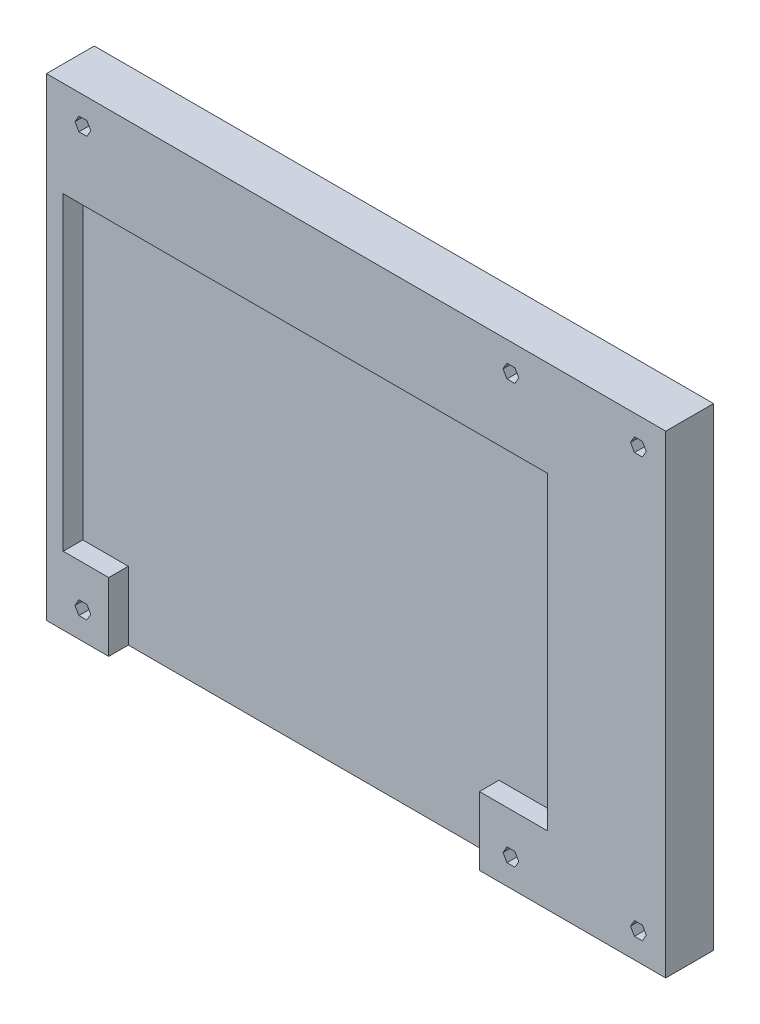
SolidWorks part; units mm, degrees
ref_plane "前视基准面" through (0, 0, 0) normal (0, 0, 1) x (1, 0, 0)
ref_plane "上视基准面" through (0, 0, 0) normal (0, 1, 0) x (1, 0, 0)
ref_plane "右视基准面" through (0, 0, 0) normal (1, 0, 0) x (0, 0, -1)
sketch "草图1" plane through (0, 0, 0) normal (0, 0, 1) x (1, 0, 0)
  line L0 (8, 104) -> (8, 0) construction
  line L1 (0, 0) -> (136, 0)
  line L2 (0, 0) -> (0, 104)
  line L3 (0, 104) -> (136, 104)
  line L4 (136, 0) -> (136, 104)
  line L5 (0, 6) -> (136, 6) construction
  line L6 (0, 98) -> (136, 98) construction
  line L7 (130, 104) -> (130, 0) construction
  line L9 (7.38, 80.5) -> (106.38, 80.5) construction
  line L10 (7.38, 80.5) -> (7.38, 23.5) construction
  line L11 (7.38, 23.5) -> (106.38, 23.5) construction
  line L12 (106.38, 80.5) -> (106.38, 23.5) construction
  line L13 (7.38, 80.5) -> (106.38, 23.5) construction
  line L14 (7.38, 23.5) -> (106.38, 80.5) construction
  line L19 (3.68, 83) -> (110.08, 83)
  line L20 (3.68, 83) -> (3.68, 15)
  line L21 (3.68, 15) -> (110.08, 15)
  line L22 (110.08, 83) -> (110.08, 15)
  line L23 (3.68, 83) -> (110.08, 15) construction
  line L24 (3.68, 15) -> (110.08, 83) construction
  line L25 (13.68, 15) -> (95.08, 15)
  line L26 (13.68, 15) -> (13.68, 0)
  line L27 (13.68, 0) -> (95.08, 0)
  line L28 (95.08, 15) -> (95.08, 0)
  line L29 (13.68, 15) -> (95.08, 0) construction
  line L30 (13.68, 0) -> (95.08, 15) construction
  line L31 (9.7321, 6) -> (8.866, 7.5)
  line L32 (8.866, 7.5) -> (7.134, 7.5)
  line L33 (7.134, 7.5) -> (6.2679, 6)
  line L34 (6.2679, 6) -> (7.134, 4.5)
  line L35 (7.134, 4.5) -> (8.866, 4.5)
  line L36 (8.866, 4.5) -> (9.7321, 6)
  line L37 (128.2679, 6) -> (129.134, 4.5)
  line L38 (129.134, 4.5) -> (130.866, 4.5)
  line L39 (130.866, 4.5) -> (131.7321, 6)
  line L40 (131.7321, 6) -> (130.866, 7.5)
  line L41 (130.866, 7.5) -> (129.134, 7.5)
  line L42 (129.134, 7.5) -> (128.2679, 6)
  line L43 (131.7321, 98) -> (130.866, 99.5)
  line L44 (130.866, 99.5) -> (129.134, 99.5)
  line L45 (129.134, 99.5) -> (128.2679, 98)
  line L46 (128.2679, 98) -> (129.134, 96.5)
  line L47 (129.134, 96.5) -> (130.866, 96.5)
  line L48 (130.866, 96.5) -> (131.7321, 98)
  line L49 (9.7321, 98) -> (8.866, 99.5)
  line L50 (8.866, 99.5) -> (7.134, 99.5)
  line L51 (7.134, 99.5) -> (6.2679, 98)
  line L52 (6.2679, 98) -> (7.134, 96.5)
  line L53 (7.134, 96.5) -> (8.866, 96.5)
  line L54 (8.866, 96.5) -> (9.7321, 98)
  line L55 (101.134, 99.5) -> (100.2679, 98)
  line L56 (100.2679, 98) -> (101.134, 96.5)
  line L57 (101.134, 96.5) -> (102.866, 96.5)
  line L58 (102.866, 96.5) -> (103.7321, 98)
  line L59 (103.7321, 98) -> (102.866, 99.5)
  line L60 (102.866, 99.5) -> (101.134, 99.5)
  line L65 (103.7321, 6) -> (102.866, 7.5)
  line L66 (102.866, 7.5) -> (101.134, 7.5)
  line L67 (101.134, 7.5) -> (100.2679, 6)
  line L68 (100.2679, 6) -> (101.134, 4.5)
  line L69 (101.134, 4.5) -> (102.866, 4.5)
  line L70 (102.866, 4.5) -> (103.7321, 6)
  circle A4 centre (8, 6) radius 1.5 construction
  circle A5 centre (130, 6) radius 1.5 construction
  circle A6 centre (130, 98) radius 1.5 construction
  circle A7 centre (8, 98) radius 1.5 construction
  circle A8 centre (102, 98) radius 1.5 construction
  circle A9 centre (102, 6) radius 1.5 construction
  point P17 (56.88, 52)
  point P18 (56.88, 52)
  point P23 (56.88, 49)
  point P28 (54.38, 7.5)
  point P29 (8, 6)
  point P30 (130, 6)
  point P31 (130, 98)
  point P32 (8, 98)
  point P36 (118.1646, 6)
  point P74 (0, 0)
  dimension "D18" = 3
  dimension "D19" = 3
  dimension "D20" = 3
  dimension "D21" = 3
  dimension "D22" = 3
  dimension "D24" = 3
  dimension "D2" = 6
  dimension "D3" = 122
  dimension "D4" = 92
  dimension "D5" = 99
  dimension "D6" = 57
  dimension "D7" = 0.62
  dimension "D8" = 17.5
  dimension "D9" = 8.5
  dimension "D10" = 2.5
  dimension "D11" = 3.7
  dimension "D12" = 3.7
  dimension "D13" = 8
  dimension "D14" = 6
  dimension "D15" = 6
  dimension "D16" = 10
  dimension "D17" = 15
  dimension "D23" = 94
  dimension "D25" = 94
extrude "凸台-拉伸1" add sketch "草图1" against normal blind 10.5 contours L1 L4 L3 L2
extrude "屏幕坑" cut sketch "草图1<3>" against normal blind 4.3 contours L22 L19 L20 L21 | L28 L21 L26 L1 region at (54.38, 7.5, 0) region at (56.88, 49, 0)
sketch "草图1<3>" plane through (0, 0, 0) normal (0, 0, 1) x (1, 0, 0) same geometry as "草图1"
extrude "六角坑" cut sketch "草图1<5>" against normal up to next contours L53 L54 L49 L50 L51 L52 | L47 L48 L43 L44 L45 L46 | L41 L42 L37 L38 L39 L40 | L35 L36 L31 L32 L33 L34 | L69 L70 L65 L66 L67 L68 | L59 L60 L55 L56 L57 L58 region at (8, 6, 0) region at (130, 6, 0) region at (130, 98, 0) region at (8, 98, 0) region at (102, 98, 0) region at (102, 6, 0)
sketch "草图1<5>" plane through (0, 0, 0) normal (0, 0, 1) x (1, 0, 0) same geometry as "草图1"
sketch "草图4" plane through (0, 0, -10.5) normal (0, 0, -1) x (-1, 0, 0)
  line L0 (-8.866, 7.5) -> (-7.134, 7.5) construction
  line L1 (-5.2679, 9.5) -> (-20.2679, 9.5)
  line L2 (-5.2679, 9.5) -> (-5.2679, 44.5)
  line L3 (-5.2679, 44.5) -> (-20.2679, 44.5)
  line L4 (-20.2679, 9.5) -> (-20.2679, 44.5)
  line L5 (-5.2679, 9.5) -> (-20.2679, 44.5) construction
  line L6 (-5.2679, 44.5) -> (-20.2679, 9.5) construction
  point P4 (-12.7679, 27)
  point P7 (-8, 7.5)
  point P8 (-12.85, 24.5)
  dimension "D1" = 2
  dimension "D2" = 35
  dimension "D3" = 15
  dimension "D4" = 1
extrude "切除-拉伸3" cut sketch "草图4" against normal blind 3 contours L2 L1 L4 L3
